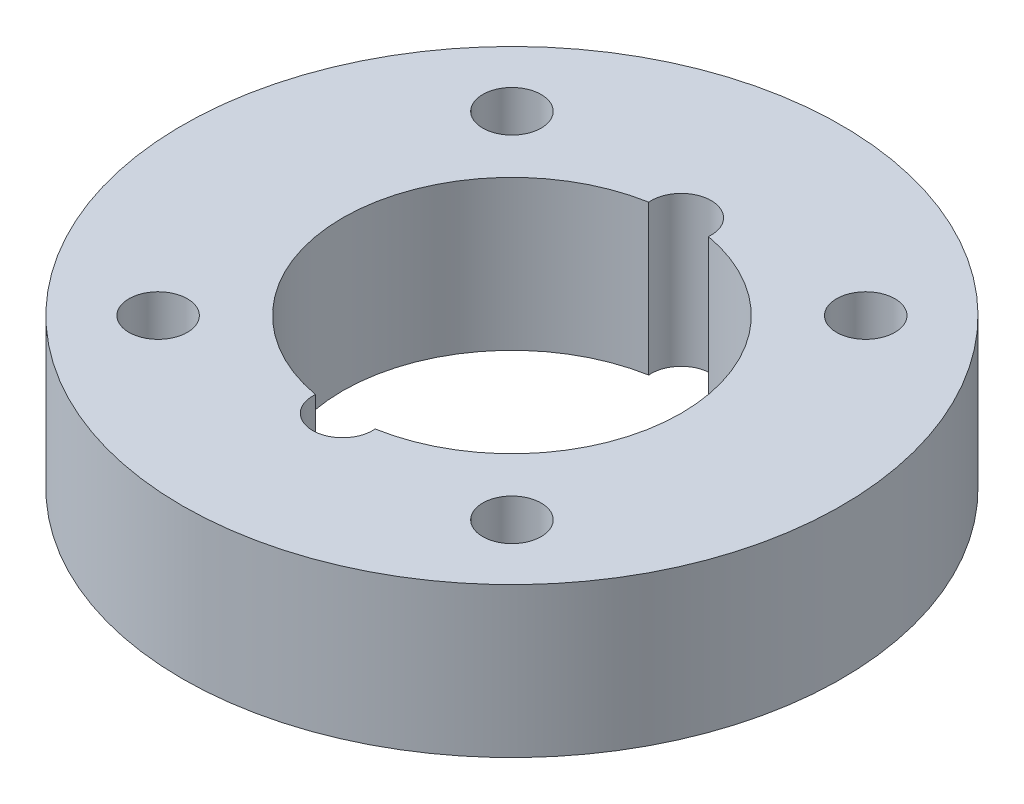
SolidWorks part; units mm, degrees
ref_plane "Front Plane" through (0, 0, 0) normal (0, 0, 1) x (1, 0, 0)
ref_plane "Top Plane" through (0, 0, 0) normal (0, 1, 0) x (1, 0, 0)
ref_plane "Right Plane" through (0, 0, 0) normal (1, 0, 0) x (0, 0, -1)
sketch "0.5in Socket" plane through (0, 0, 0) normal (0, 1, 0) x (1, 0, 0)
  line L0 (0, 0) -> (-14.997, 14.997) construction
  line L1 (14.997, -14.997) -> (0, 0) construction
  line L2 (-14.997, -14.997) -> (0, 0) construction
  line L3 (0, 0) -> (14.997, 14.997) construction
  line L4 (0, 0) -> (0, -14.351) construction
  circle A0 centre (0, 0) radius 27.94
  circle A1 centre (0, 0) radius 2.5527
  arc A2 (-2.53, 14.1262) -> (2.53, 14.1262) centre (0, 14.351) cw
  arc A3 (2.53, 14.1262) -> (2.53, -14.1262) centre (0, 0) cw
  arc A4 (2.53, -14.1262) -> (-2.53, -14.1262) centre (0, -14.351) cw
  arc A5 (-2.53, -14.1262) -> (-2.53, 14.1262) centre (0, 0) cw
  circle A6 centre (14.997, -14.997) radius 2.475
  circle A7 centre (14.997, 14.997) radius 2.475
  circle A8 centre (-14.997, 14.997) radius 2.475
  circle A9 centre (-14.997, -14.997) radius 2.475
  point P4 (0, 0)
  point P8 (0, -14.351)
  point P9 (0, 0)
  point P10 (0, 14.351)
  point P16 (0, 0)
  dimension "D1" = 55.88
  dimension "D2" = 5.1054
  dimension "D4" = 14.351
  dimension "D5" = 14.351
  dimension "D7" = 2.54
  dimension "D8" = 2.54
  dimension "D9" = 4.95
  dimension "D10" = 4.95
  dimension "D11" = 4.95
  dimension "D12" = 4.95
  dimension "D13" = 21.209
  dimension "D17" = 90
  dimension "D3" = 28.702
  dimension "D6" = 14.351
  dimension "D14" = 21.209
  dimension "D15" = 21.209
  dimension "D16" = 21.209
  dimension "D18" = 90
  dimension "D19" = 90
  dimension "D20" = 45
extrude "Boss-Extrude1" add sketch "0.5in Socket" along normal blind 12.7 contours A0 A9 A8 A7 A6 A4 A5 A2 A3 region at (-27.1497, 0, 0)
